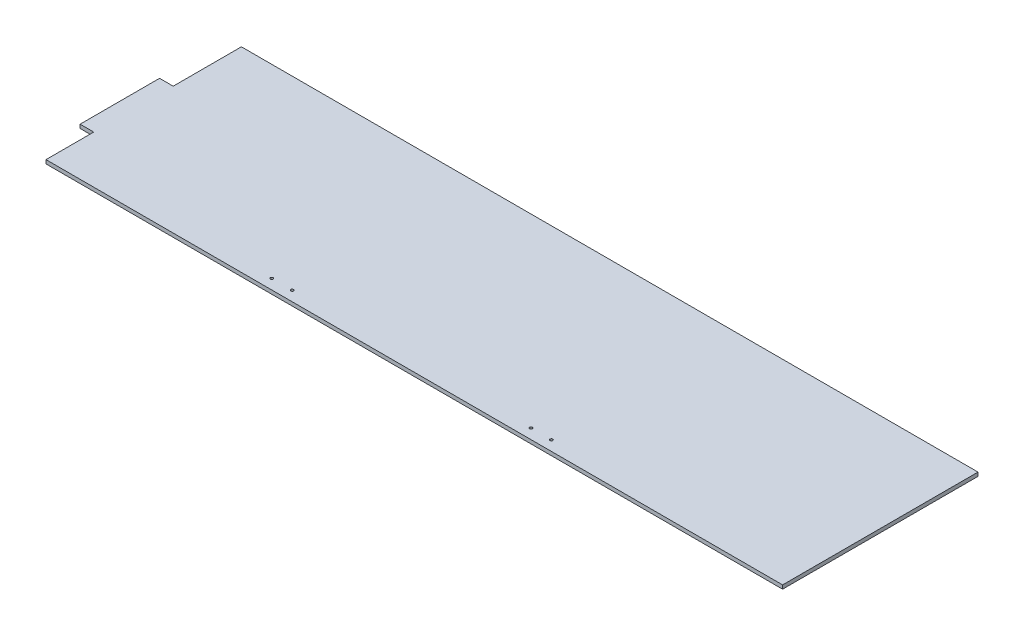
SolidWorks part; units mm, degrees
ref_plane "Front Plane" through (0, 0, 0) normal (0, 0, 1) x (1, 0, 0)
ref_plane "Top Plane" through (0, 0, 0) normal (0, 1, 0) x (1, 0, 0)
ref_plane "Right Plane" through (0, 0, 0) normal (1, 0, 0) x (0, 0, -1)
sketch "Sketch1" plane through (0, 0, 0) normal (0, 1, 0) x (1, 0, 0)
  line L0 (-255.3044, 24.1708) -> (-245.3044, 24.1708)
  line L1 (-245.3044, 74.1708) -> (294.6956, 74.1708)
  line L2 (-245.3044, 74.1708) -> (-245.3044, 24.1708)
  line L3 (-245.3044, -69.0805) -> (294.6956, -69.0805)
  line L4 (294.6956, 74.1708) -> (294.6956, -69.0805)
  line L5 (-245.3044, 74.1708) -> (294.6956, -69.0805) construction
  line L6 (-245.3044, -69.0805) -> (294.6956, 74.1708) construction
  line L7 (-255.3044, 24.1708) -> (-255.3044, -34.0805)
  line L8 (-255.3044, -34.0805) -> (-245.3044, -34.0805)
  line L9 (-245.3044, -34.0805) -> (-245.3044, -69.0805)
  line L10 (-245.3044, 22.6702) -> (-245.3044, 24.1708) construction
  line L11 (-245.3044, -15.4298) -> (-245.3044, -34.0805) construction
  line L12 (-87.1562, -61.7545) -> (-72.1562, -61.7545) construction
  line L13 (-72.1562, -61.7545) -> (102.8438, -61.7545) construction
  line L14 (102.8438, -61.7545) -> (117.8438, -61.7545) construction
  line L15 (-241.1475, -69.0805) -> (273.4525, -69.0805) construction
  circle A0 centre (117.8438, -61.7545) radius 1
  circle A1 centre (102.8438, -61.7545) radius 1
  circle A3 centre (-87.1562, -61.7545) radius 1
  circle A4 centre (-72.1562, -61.7545) radius 1
  point P4 (24.6956, 2.5451)
  dimension "D1" = 50
  dimension "D2" = 35
  dimension "D3" = 15
  dimension "D4" = 175
  dimension "D5" = 15
  dimension "D6" = 10
  dimension "D7" = 540
  dimension "D8" = 143.2513
extrude "Boss-Extrude1" add sketch "Sketch1" along normal blind 2.7432 from offset 2 contours L8 L9 L3 L4 L1 L2 L0 L7 A4 A3 A1 A0 region at (22.6415, 0, -2.4994)
